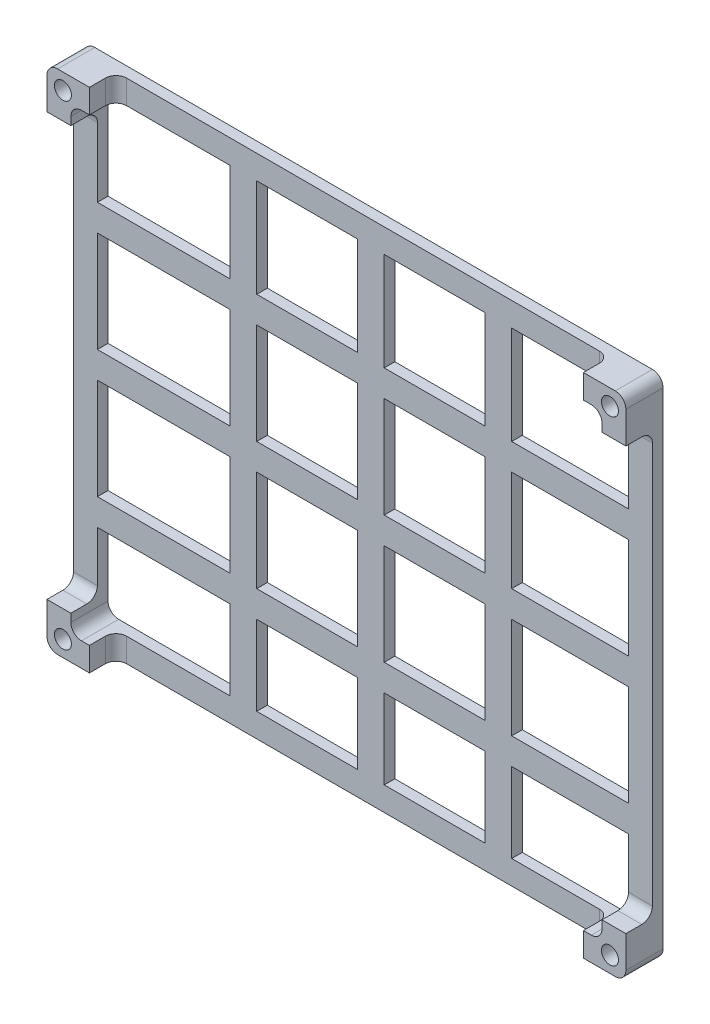
SolidWorks part; units mm, degrees
ref_plane "Front Plane" through (0, 0, 0) normal (0, 0, 1) x (1, 0, 0)
ref_plane "Top Plane" through (0, 0, 0) normal (0, 1, 0) x (1, 0, 0)
ref_plane "Right Plane" through (0, 0, 0) normal (1, 0, 0) x (0, 0, -1)
sketch "Base_Sketch" plane through (0, 0, 0) normal (0, 0, 1) x (1, 0, 0)
  line L0 (0, 20.3972) -> (0, -24.9578) construction
  line L1 (-17.5167, 0) -> (15.6483, 0) construction
  line L2 (-54.5, 47.75) -> (-54.5, -47.75)
  line L3 (-51.5, 44.75) -> (51.5, 44.75) construction
  line L4 (-51.5, 44.75) -> (-51.5, -44.75) construction
  line L5 (-51.5, -44.75) -> (51.5, -44.75) construction
  line L6 (51.5, 44.75) -> (51.5, -44.75) construction
  line L7 (-51.5, 44.75) -> (51.5, -44.75) construction
  line L8 (-51.5, -44.75) -> (51.5, 44.75) construction
  line L9 (-54.5, -47.75) -> (54.5, -47.75)
  line L10 (54.5, 47.75) -> (54.5, -47.75)
  line L11 (-54.5, 47.75) -> (54.5, 47.75)
  line L12 (-50, 43.25) -> (-50, -43.25)
  line L13 (-50, -43.25) -> (50, -43.25)
  line L14 (50, 43.25) -> (50, -43.25)
  line L15 (-50, 43.25) -> (50, 43.25)
  line L16 (-25, -43.25) -> (-25, 43.25)
  line L18 (-20, 43.25) -> (-20, -43.25)
  line L20 (-1, -43.25) -> (-1, 43.25)
  line L21 (4, 43.25) -> (4, -43.25)
  line L22 (23, -43.25) -> (23, 43.25)
  line L23 (28, 43.25) -> (28, -43.25)
  line L24 (-25, -43.25) -> (-1, -43.25) construction
  line L25 (-50, -28.25) -> (54.5, -28.25)
  line L26 (-50, -23.25) -> (54.5, -23.25)
  line L27 (-50, 0.75) -> (54.5, 0.75)
  line L28 (-50, -4.25) -> (54.5, -4.25)
  line L29 (-50, 24.75) -> (54.5, 24.75)
  line L30 (-50, 19.75) -> (54.5, 19.75)
  line L31 (-50, -23.25) -> (-50, 0.75) construction
  line L32 (46.5, -43.25) -> (46.5, -47.75)
  line L33 (50, -39.75) -> (54.5, -39.75)
  line L34 (-46.5, -43.25) -> (-46.5, -47.75)
  line L35 (-50, -39.75) -> (-54.5, -39.75)
  line L36 (-50, 39.75) -> (-54.5, 39.75)
  line L37 (-46.5, 43.25) -> (-46.5, 47.75)
  line L38 (50, 39.75) -> (54.5, 39.75)
  line L39 (46.5, 43.25) -> (46.5, 47.75)
  circle A0 centre (-51.5, 44.75) radius 1.6
  circle A1 centre (51.5, 44.75) radius 1.6
  circle A2 centre (51.5, -44.75) radius 1.6
  circle A3 centre (-51.5, -44.75) radius 1.6
  point P4 (0, 0)
  point P52 (0, 0)
  dimension "D1" = 3.2
  dimension "D2" = 103
  dimension "D3" = 89.5
  dimension "D6" = 5
  dimension "D7" = 25
  dimension "D9" = 24
  dimension "D10" = 5
  dimension "D11" = 15
  dimension "D13" = 24
  dimension "D14" = 5
  dimension "D15" = 5
  dimension "D4" = 3
  dimension "D5" = 1.5
  dimension "D8" = 3
  dimension "D12" = 3
extrude "Boss-Extrude1" add sketch "Base_Sketch" along normal blind 2 contours L13 L34 L9 L32 | L12 L35 L2 L9 L34 L13 A3 | L12 L36 L2 L35 | L26 L12 L25 L16 | L26 L16 L25 L18 | L25 L16 L13 L18 | L26 L18 L25 L20 | L26 L20 L25 L21 | L25 L20 L13 L21 | L26 L21 L25 L22 | L26 L22 L25 L23 | L25 L22 L13 L23 | L26 L23 L25 L14 | L26 L14 L25 L10 | L14 L33 L10 L25 | L33 L14 L13 L32 L9 L10 A2 | L28 L14 L26 L10 | L14 L28 L10 L27 | L23 L28 L14 L27 | L22 L28 L23 L27 | L28 L22 L26 L23 | L30 L22 L27 L23 | L21 L28 L22 L27 | L20 L28 L21 L27 | L28 L20 L26 L21 | L30 L14 L27 L10 | L14 L30 L10 L29 | L38 L14 L29 L10 | L39 L15 L14 L38 L10 L11 A1 | L15 L39 L11 L37 | L23 L30 L14 L29 | L22 L29 L23 L15 | L22 L30 L23 L29 | L21 L30 L22 L29 | L20 L30 L21 L29 | L20 L29 L21 L15 | L30 L20 L27 L21 | L18 L30 L20 L29 | L18 L28 L20 L27 | L16 L28 L18 L27 | L15 L37 L11 L2 L36 L12 A0 | L12 L30 L16 L29 | L16 L30 L18 L29 | L16 L29 L18 L15 | L30 L16 L27 L18 | L12 L28 L16 L27 | L28 L16 L26 L18 region at (-50.5, 47.6369, 0) region at (-52.25, 0, 0) region at (0, 45.5, 0) region at (-52.25, -39.8631, 0) region at (50.5, 47.6369, 0) region at (-37.5, 22.25, 0) region at (-22.5, 34, 0) region at (0, -45.5, 0) region at (-37.5, -25.75, 0) region at (-22.5, 22.25, 0) region at (52.25, 32.25, 0) region at (25.5, 34, 0) region at (46.6131, -45.5, 0) region at (-22.5, -35.75, 0) region at (-22.5, -25.75, 0) region at (-37.5, -1.75, 0) region at (-22.5, 10.25, 0) region at (-10.5, 22.25, 0) region at (52.25, 22.25, 0) region at (39, 22.25, 0) region at (25.5, 22.25, 0) region at (1.5, 34, 0) region at (-22.5, -13.75, 0) region at (-10.5, -25.75, 0) region at (-22.5, -1.75, 0) region at (1.5, 22.25, 0) region at (52.25, 10.25, 0) region at (13.5, 22.25, 0) region at (25.5, 10.25, 0) region at (52.25, -34, 0) region at (25.5, -35.75, 0) region at (1.5, -35.75, 0) region at (1.5, -25.75, 0) region at (-10.5, -1.75, 0) region at (1.5, 10.25, 0) region at (52.25, -1.75, 0) region at (39, -1.75, 0) region at (25.5, -1.75, 0) region at (52.25, -25.75, 0) region at (25.5, -25.75, 0) region at (39, -25.75, 0) region at (1.5, -13.75, 0) region at (13.5, -25.75, 0) region at (1.5, -1.75, 0) region at (52.25, -13.75, 0) region at (13.5, -1.75, 0) region at (25.5, -13.75, 0)
extrude "Boss-Extrude2" add sketch "Sketch1<7>" along normal blind 5 from surface contours L15 L37 L11 L2 L36 L12 A0 | L39 L15 L14 L38 L10 L11 A1 | L12 L35 L2 L9 L34 L13 A3 | L33 L14 L13 L32 L9 L10 A2 region at (-50.5, 47.6369, 0) region at (-52.25, -39.8631, 0) region at (50.5, 47.6369, 0) region at (46.6131, -45.5, 0) starting at face at (39, 10.25, 2)
sketch "Sketch1<7>" plane through (0, 0, 0) normal (0, 0, 1) x (1, 0, 0) same geometry as "Base_Sketch"
fillet "Fillet1" radius 2 16 edges at (54.5, 47.75, 3.5) (-54.5, 47.75, 3.5) (-54.5, -47.75, 3.5) (-50, -43.25, 3.5) (50, -43.25, 3.5) (54.5, -47.75, 3.5) (-52.25, -39.75, 2) (-46.5, -45.5, 2) (46.5, -45.5, 2) (52.25, -39.75, 2) (46.5, 45.5, 2) (52.25, 39.75, 2) (-46.5, 45.5, 2) (-52.25, 39.75, 2) (-50, 43.25, 3.5) (50, 43.25, 3.5)
